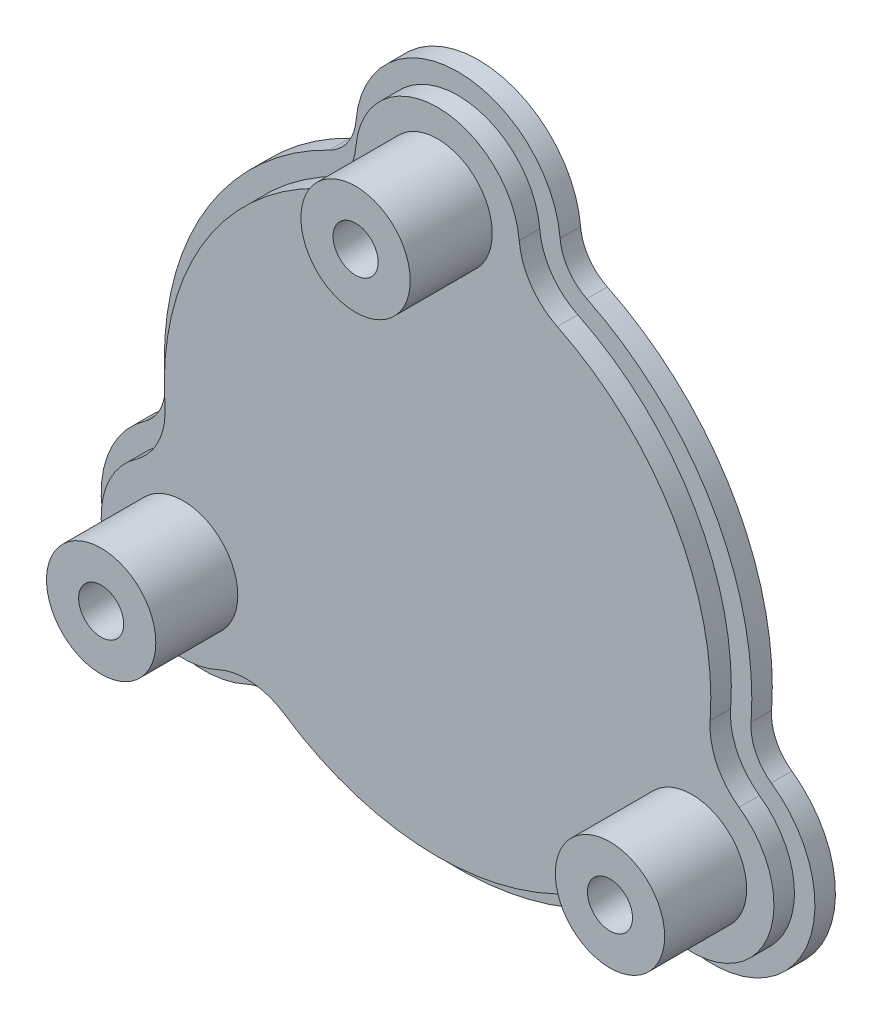
SolidWorks part; units mm, degrees
ref_plane "Front Plane" through (0, 0, 0) normal (0, 0, 1) x (1, 0, 0)
ref_plane "Top Plane" through (0, 0, 0) normal (0, 1, 0) x (1, 0, 0)
ref_plane "Right Plane" through (0, 0, 0) normal (1, 0, 0) x (0, 0, -1)
sketch "Sketch1" plane through (0, 0, 0) normal (0, 0, 1) x (1, 0, 0)
  line L0 (0, 73.3218) -> (0, -73.3218) construction
  line L1 (-500, 0) -> (24500, 0) construction
  line L2 (0, 0) -> (-37.2391, -21.5) construction
  line L3 (0, 0) -> (37.2391, -21.5) construction
  arc A0 (-18.8462, 38.65) -> (-42.895, -3.0038) centre (0, 0) ccw
  arc A1 (14.9415, 44.324) -> (-14.9415, 44.324) centre (0, 43) ccw
  arc A2 (18.8462, 38.65) -> (14.9415, 44.324) centre (21.9141, 44.9419) cw
  arc A3 (-18.8462, 38.65) -> (-14.9415, 44.324) centre (-21.9141, 44.9419) ccw
  arc A4 (-17.5313, 35.9535) -> (-39.9023, -2.7942) centre (0, 0) ccw
  arc A5 (17.5313, 35.9535) -> (11.9532, 44.0592) centre (21.9141, 44.9419) cw
  arc A6 (11.9532, 44.0592) -> (-11.9532, 44.0592) centre (0, 43) ccw
  arc A7 (-17.5313, 35.9535) -> (-11.9532, 44.0592) centre (-21.9141, 44.9419) ccw
  circle A8 centre (0, 43) radius 8
  circle A9 centre (0, 43) radius 3.3
  circle A10 centre (37.2391, -21.5) radius 3.3
  circle A11 centre (37.2391, -21.5) radius 8
  arc A12 (39.9023, -2.7942) -> (44.133, -11.6779) centre (49.8779, -3.4927) ccw
  arc A13 (32.1798, -32.3813) -> (44.133, -11.6779) centre (37.2391, -21.5) ccw
  arc A14 (30.915, -35.1017) -> (45.8564, -9.2223) centre (37.2391, -21.5) ccw
  arc A15 (42.895, -3.0038) -> (45.8564, -9.2223) centre (49.8779, -3.4927) ccw
  arc A16 (22.371, -33.1593) -> (32.1798, -32.3813) centre (27.9637, -41.4491) cw
  arc A17 (24.0488, -35.6462) -> (30.915, -35.1017) centre (27.9637, -41.4491) cw
  circle A18 centre (-37.2391, -21.5) radius 3.3
  circle A19 centre (-37.2391, -21.5) radius 8
  arc A20 (-22.371, -33.1593) -> (-32.1798, -32.3813) centre (-27.9637, -41.4491) ccw
  arc A21 (-44.133, -11.6779) -> (-32.1798, -32.3813) centre (-37.2391, -21.5) ccw
  arc A22 (-45.8564, -9.2223) -> (-30.915, -35.1017) centre (-37.2391, -21.5) ccw
  arc A23 (-24.0488, -35.6462) -> (-30.915, -35.1017) centre (-27.9637, -41.4491) ccw
  arc A24 (-39.9023, -2.7942) -> (-44.133, -11.6779) centre (-49.8779, -3.4927) cw
  arc A25 (-42.895, -3.0038) -> (-45.8564, -9.2223) centre (-49.8779, -3.4927) cw
  arc A26 (-24.0488, -35.6462) -> (24.0488, -35.6462) centre (0, 0) ccw
  arc A27 (-22.371, -33.1593) -> (22.371, -33.1593) centre (0, 0) ccw
  arc A28 (-18.8462, 38.65) -> (18.8462, 38.65) centre (0, 0) ccw construction
  circle A29 centre (0, 0) radius 43 construction
  arc A30 (-17.5313, 35.9535) -> (17.5313, 35.9535) centre (0, 0) ccw construction
  arc A31 (42.895, -3.0038) -> (18.8462, 38.65) centre (0, 0) ccw
  arc A33 (39.9023, -2.7942) -> (17.5313, 35.9535) centre (0, 0) ccw
  point P4 (0, 0)
  point P59 (0, 0)
  dimension "D1" = 86
  dimension "D2" = 15
  dimension "D3" = 7
  dimension "D5" = 16
  dimension "D4" = 3
  dimension "D6" = 6.6
  dimension "D9" = 86
  dimension "D8" = 120
  dimension "D7" = 3
extrude "Boss-Extrude1" add sketch "Sketch1" along normal blind 3 contours A15 A31 A2 A1 A3 A0 A25 A22 A23 A26 A17 A14 A33 A12 A13 A16 A27 A20 A21 A24 A4 A7 A6 A5 region at (-14.9506, 40.1497, 0)
extrude "Boss-Extrude2" add sketch "Sketch1<3>" along normal blind 6 contours A12 A33 A5 A6 A7 A4 A24 A21 A20 A27 A16 A13 A19 A11 A8 region at (0, 0, 0)
sketch "Sketch1<3>" plane through (0, 0, 0) normal (0, 0, 1) x (1, 0, 0) same geometry as "Sketch1"
extrude "Boss-Extrude4" add sketch "Sketch1<5>" along normal blind 18 contours A11 A10 | A19 A18 | A8 A9 region at (-7.7737, 43, 0) region at (29.4654, -21.5, 0) region at (-45.0128, -21.5, 0)
sketch "Sketch1<5>" plane through (0, 0, 0) normal (0, 0, 1) x (1, 0, 0) same geometry as "Sketch1"
